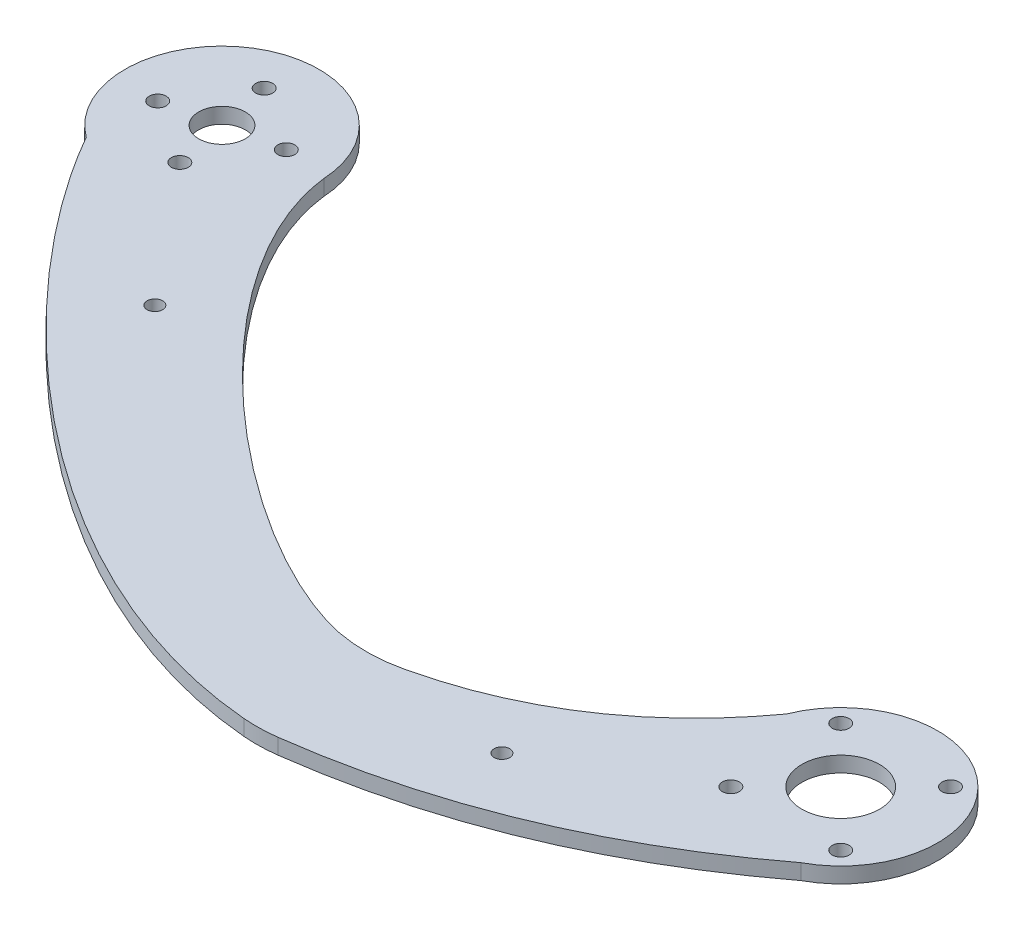
SolidWorks part; units mm, degrees
material "1060 Alloy"
ref_plane "Front" through (0, 0, 0) normal (0, 0, 1) x (1, 0, 0)
ref_plane "Top" through (0, 0, 0) normal (0, 1, 0) x (1, 0, 0)
ref_plane "Right" through (0, 0, 0) normal (1, 0, 0) x (0, 0, -1)
sketch "Sketch2" plane through (0, 0, 0) normal (0, 1, 0) x (1, 0, 0)
  point P0 (0, 0)
  line B0 (-70.9851, 36.1523) -> (-113.5823, 33.9244)
  arc B1 (5.8927, -11.0239) -> (-11.6176, 4.6132) centre (0, 0) ccw
  arc B2 (-101.0993, 34.5773) -> (-120.9882, 23.8546) centre (-113.5823, 33.9244) ccw
  spline B3 degree 3 poles (-44.5149, -15.6481) (-60.4932, -16.621) (-98.7194, 13.994) (-101.0993, 34.5773) knots 0 0 0 0 1 1 1 1
  spline B4 degree 2 poles (5.8927, -11.0239) (-16.2083, -27.8197) (-43.715, -30.9419) knots 0 0 0 1 1 1
  spline B5 degree 3 poles (-43.715, -30.9419) (-74.6559, -29.7722) (-107.9347, 0.9093) (-120.9882, 23.8546) knots 0 0 0 0 1 1 1 1
  spline B6 degree 2 poles (-44.5149, -15.6481) (-23.755, -12.0499) (-11.6176, 4.6132) knots 0 0 0 1 1 1
sketch_block_instance "Block5-1"
sketch_block "Block5" parameters "D1"=25, "D14"=79.1954, "D15"=48.0238, "D17"=92.8889, "D18"=42.1388, "D19"=62.1612, "D2"=5.3089, "D3"=16.6697, "D4"=25.1002, "D5"=50.5803, "D6"=74.3089, "D7"=104.4643, "D8"=116.9643, "D9"=124.8861, "D10"=135.8089, "D11"=34.5967, "D12"=39.8104, "D13"=51.127, "D16"=68.4269
extrude "Boss-Extrude1" add sketch "Sketch2" along normal blind 2 contours B5 B4 B1 B6 B3 B2 region at (-18.1336, 0, 22.9214)
fillet "Fillet2" radius 20 1 edges at (-44.5149, 1, 15.6481)
fillet "Fillet3" radius 20 1 edges at (-43.715, 1, 30.9419)
ref_plane "Plane1" through (0, 2, 0) normal (0, 1, 0) x (1, 0, 0)
sketch "Sketch3" plane through (0, 2, 0) normal (0, 1, 0) x (1, 0, 0)
  line L0 (0, 0) -> (0, 56.3072) construction
  line L1 (-7.0711, 7.0711) -> (0, 0) construction
  line L2 (-113.5823, 33.9244) -> (0, 0) construction
  line L3 (-56.7911, 16.9622) -> (-30.8992, 103.6508) construction
  line L4 (-103.7915, 35.9592) -> (-113.5823, 33.9244) construction
  line L5 (-115.6171, 43.7152) -> (-113.5823, 33.9244) construction
  line L6 (-103.7915, 35.9592) -> (-113.5823, 33.9244) construction
  line L7 (-111.5474, 24.1336) -> (-113.5823, 33.9244) construction
  line L8 (-123.3731, 31.8896) -> (-113.5823, 33.9244) construction
  circle A0 centre (0, 0) radius 5
  circle A1 centre (-7.0711, 7.0711) radius 1.09
  circle A2 centre (7.0711, 7.0711) radius 1.09
  circle A3 centre (7.0711, -7.0711) radius 1.09
  circle A4 centre (-7.0711, -7.0711) radius 1.09
  circle A5 centre (-113.5823, 33.9244) radius 3
  circle A6 centre (-106.7287, 35.3488) radius 1.09
  circle A7 centre (-112.1579, 27.0709) radius 1.09
  circle A8 centre (-120.4358, 32.5001) radius 1.09
  circle A10 centre (-115.0066, 40.778) radius 1.09
  point P8 (-56.7911, 16.9622)
  point P15 (0, 0)
  point P35 (-113.5823, 33.9244)
  dimension "D1" = 10
  dimension "D2" = 2.18
  dimension "D6" = 6
  dimension "D7" = 2.18
  dimension "D8" = 7
  dimension "D3" = 45
  dimension "D4" = 10
  dimension "D5" = 4
  dimension "D9" = 4
extrude "Cut-Extrude2" cut sketch "Sketch3" against normal blind 10
sketch "Sketch4" plane through (0, 2, 0) normal (0, 1, 0) x (1, 0, 0)
  line L0 (-113.5823, 33.9244) -> (-69.4661, -34.4033) construction
  line L1 (0, 0) -> (-63.0101, -44.4968) construction
  circle A0 centre (-97.8402, 9.543) radius 1
  circle A1 centre (-25.5617, -18.0513) radius 1
  dimension "D1" = 2
  dimension "D2" = 25.5617
  dimension "D3" = 97.8402
  dimension "D4" = 9.543
  dimension "D5" = 18.0513
extrude "Cut-Extrude3" cut sketch "Sketch4" against normal blind 10
